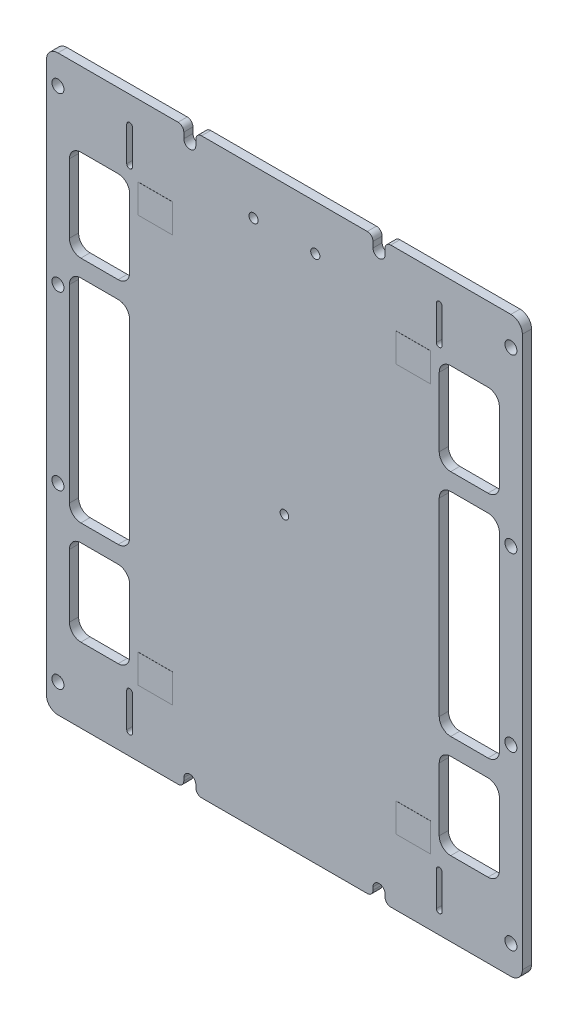
SolidWorks part; units mm, degrees
material "FR4_stuffedProtoboard"
ref_plane "Front Plane" through (0, 0, 0) normal (0, 0, 1) x (1, 0, 0)
ref_plane "Top Plane" through (0, 0, 0) normal (0, 1, 0) x (1, 0, 0)
ref_plane "Right Plane" through (0, 0, 0) normal (1, 0, 0) x (0, 0, -1)
sketch "Sketch1" plane through (0, 0, 0) normal (0, 0, 1) x (1, 0, 0)
  line L1 (-39.5, -50) -> (39.5, -50)
  line L2 (-41.5, -48) -> (-41.5, 48)
  line L3 (-39.5, 50) -> (39.5, 50)
  line L4 (41.5, -48) -> (41.5, 48)
  line L5 (-41.5, -50) -> (41.5, 50) construction
  line L6 (-41.5, 50) -> (41.5, -50) construction
  arc A0 (-39.5, -50) -> (-41.5, -48) centre (-39.5, -48) cw
  arc A1 (39.5, -50) -> (41.5, -48) centre (39.5, -48) ccw
  arc A2 (39.5, 50) -> (41.5, 48) centre (39.5, 48) cw
  arc A3 (-41.5, 48) -> (-39.5, 50) centre (-39.5, 48) cw
  point P0 (0, 0)
  dimension "D3" = 2
  dimension "D1" = 100
  dimension "D2" = 83
extrude "boardOutline" add sketch "Sketch1" along normal blind 1.6
sketch "Sketch2" plane through (0, 0, 1.6) normal (0, 0, 1) x (1, 0, 0)
  line L0 (39.5, 50) -> (-39.5, 50) construction
  line L1 (-41.5, 48) -> (-41.5, -48) construction
  line L2 (-5.385, 42.1) -> (5.385, 42.1) construction
  line L3 (-38, 44.2) -> (-38, 4.2) construction
  line L4 (0, 42.1) -> (0, 50) construction
  circle A0 centre (0, 0) radius 0.75
  circle A1 centre (-38, 44.2) radius 1.05 construction
  circle A2 centre (37.5, 44.2) radius 1.05 construction
  circle A3 centre (37.5, 4.2) radius 1.05 construction
  circle A4 centre (37.5, -35.8) radius 1.05 construction
  circle A5 centre (-38, 4.2) radius 1.05 construction
  circle A6 centre (-38, -35.8) radius 1.05 construction
  circle A7 centre (-5.385, 42.1) radius 0.8
  circle A8 centre (5.385, 42.1) radius 0.8
  dimension "D1" = 1.5
  dimension "D2" = 2.1
  dimension "D9" = 10.77
  dimension "D7" = 1.6
  dimension "D11" = 7.9
  dimension "D3" = 5.8
  dimension "D4" = 3.5
  dimension "D8" = 40
  dimension "D10" = 37.5
  dimension "D5" = 2
  dimension "D6" = 3
extrude "componentHoles" cut sketch "Sketch2" against normal through all
sketch "Sketch4" plane through (0, 0, 1.6) normal (0, 0, 1) x (1, 0, 0)
  line L0 (-27, 39.25) -> (-27, 45.25) construction
  line L1 (-27.5, 39.25) -> (-27.5, 45.25)
  line L2 (-26.5, 39.25) -> (-26.5, 45.25)
  line L3 (39.5, 50) -> (-39.5, 50) construction
  line L4 (-41.5, 48) -> (-41.5, -48) construction
  line L5 (27, 39.25) -> (27, 45.25) construction
  line L6 (26.5, 39.25) -> (26.5, 45.25)
  line L7 (27.5, 39.25) -> (27.5, 45.25)
  line L8 (27, -46.25) -> (27, -40.25) construction
  line L9 (26.5, -46.25) -> (26.5, -40.25)
  line L10 (27.5, -46.25) -> (27.5, -40.25)
  line L11 (-27, -46.25) -> (-27, -40.25) construction
  line L12 (-27.5, -46.25) -> (-27.5, -40.25)
  line L13 (-26.5, -46.25) -> (-26.5, -40.25)
  line L14 (-27, 39.25) -> (27, 39.25) construction
  line L15 (0, 39.25) -> (0, 50) construction
  arc A0 (-27.5, 39.25) -> (-26.5, 39.25) centre (-27, 39.25) ccw
  arc A1 (-26.5, 45.25) -> (-27.5, 45.25) centre (-27, 45.25) ccw
  arc A2 (26.5, 39.25) -> (27.5, 39.25) centre (27, 39.25) ccw
  arc A3 (27.5, 45.25) -> (26.5, 45.25) centre (27, 45.25) ccw
  arc A4 (26.5, -46.25) -> (27.5, -46.25) centre (27, -46.25) ccw
  arc A5 (27.5, -40.25) -> (26.5, -40.25) centre (27, -40.25) ccw
  arc A6 (-27.5, -46.25) -> (-26.5, -46.25) centre (-27, -46.25) ccw
  arc A7 (-26.5, -40.25) -> (-27.5, -40.25) centre (-27, -40.25) ccw
  point P2 (-27, 42.25)
  point P16 (27, 42.25)
  point P23 (27, -43.25)
  point P30 (-27, -43.25)
  dimension "D1" = 4.75
  dimension "D2" = 14
  dimension "D3" = 1
  dimension "D4" = 6
  dimension "D7" = 54
  dimension "D9" = 79.5
  dimension "D5" = 2
  dimension "D6" = 2
extrude "solarCellContactHoles" cut sketch "Sketch4" against normal blind 1.6
sketch "FrameLattice" plane through (0, 0, 0) normal (0, 0, 1) x (1, 0, 0)
  line L4 (-13, -19) -> (13, -19)
  line L5 (15, -17) -> (15, 16)
  line L6 (13, 18) -> (-13, 18)
  line L7 (-15, 16) -> (-15, -17)
  line L8 (-13, -19) -> (13, -19)
  line L9 (15, -17) -> (15, 16)
  line L10 (13, 18) -> (-13, 18)
  line L11 (-15, 16) -> (-15, -17)
  line L12 (-13, -92) -> (13, -92)
  line L13 (15, -90) -> (15, -69)
  line L14 (13, -67) -> (-13, -67)
  line L15 (-15, -69) -> (-15, -90)
  line L16 (-13, -92) -> (13, -92)
  line L17 (15, -90) -> (15, -69)
  line L18 (13, -67) -> (-13, -67)
  line L19 (-15, -69) -> (-15, -90)
  line L20 (-35.5, -132) -> (-20, -132)
  line L21 (-18, -130) -> (-18, -97)
  line L22 (-20, -95) -> (-35.5, -95)
  line L23 (-37.5, -97) -> (-37.5, -130)
  line L24 (-35.5, -132) -> (-20, -132)
  line L25 (-18, -130) -> (-18, -97)
  line L26 (-20, -95) -> (-35.5, -95)
  line L27 (-37.5, -97) -> (-37.5, -130)
  line L28 (20, -160) -> (35.5, -160)
  line L29 (37.5, -158) -> (37.5, -137)
  line L30 (35.5, -135) -> (20, -135)
  line L31 (18, -137) -> (18, -158)
  line L32 (20, -160) -> (35.5, -160)
  line L33 (37.5, -158) -> (37.5, -137)
  line L34 (35.5, -135) -> (20, -135)
  line L35 (18, -137) -> (18, -158)
  line L36 (20, -92) -> (35.5, -92)
  line L37 (37.5, -90) -> (37.5, -69)
  line L38 (35.5, -67) -> (20, -67)
  line L39 (18, -69) -> (18, -90)
  line L40 (20, -92) -> (35.5, -92)
  line L41 (37.5, -90) -> (37.5, -69)
  line L42 (35.5, -67) -> (20, -67)
  line L43 (18, -69) -> (18, -90)
  line L44 (-35.5, -92) -> (-20, -92)
  line L45 (-18, -90) -> (-18, -69)
  line L46 (-20, -67) -> (-35.5, -67)
  line L47 (-37.5, -69) -> (-37.5, -90)
  line L48 (-35.5, -92) -> (-20, -92)
  line L49 (-18, -90) -> (-18, -69)
  line L50 (-20, -67) -> (-35.5, -67)
  line L51 (-37.5, -69) -> (-37.5, -90)
  line L52 (20, -132) -> (35.5, -132)
  line L53 (37.5, -130) -> (37.5, -97)
  line L54 (35.5, -95) -> (20, -95)
  line L55 (18, -97) -> (18, -130)
  line L56 (20, -132) -> (35.5, -132)
  line L57 (37.5, -130) -> (37.5, -97)
  line L58 (35.5, -95) -> (20, -95)
  line L59 (18, -97) -> (18, -130)
  line L60 (-13, -160) -> (13, -160)
  line L61 (15, -158) -> (15, -137)
  line L62 (13, -135) -> (-13, -135)
  line L63 (-15, -137) -> (-15, -158)
  line L65 (15, -158) -> (15, -137)
  line L66 (13, -135) -> (-13, -135)
  line L67 (-15, -137) -> (-15, -158)
  line L68 (-26.75, -62) -> (-26.75, -52)
  line L69 (-28.75, -50) -> (-35, -50)
  line L70 (-37, -52) -> (-37, -62)
  line L71 (-35, -64) -> (-28.75, -64)
  line L72 (-26.75, -62) -> (-26.75, -52)
  line L73 (-28.75, -50) -> (-35, -50)
  line L74 (-37, -52) -> (-37, -62)
  line L75 (-35, -64) -> (-28.75, -64)
  line L76 (-35.5, -160) -> (-20, -160)
  line L77 (-18, -158) -> (-18, -137)
  line L78 (-20, -135) -> (-35.5, -135)
  line L79 (-37.5, -137) -> (-37.5, -158)
  line L80 (-35.5, -160) -> (-20, -160)
  line L81 (-18, -158) -> (-18, -137)
  line L82 (-20, -135) -> (-35.5, -135)
  line L83 (-37.5, -137) -> (-37.5, -158)
  line L84 (-13, -132) -> (13, -132)
  line L85 (15, -130) -> (15, -97)
  line L86 (13, -95) -> (-13, -95)
  line L87 (-15, -97) -> (-15, -130)
  line L88 (-13, -132) -> (13, -132)
  line L89 (15, -130) -> (15, -97)
  line L90 (13, -95) -> (-13, -95)
  line L91 (-15, -97) -> (-15, -130)
  line L92 (-35.5, -19) -> (-20, -19)
  line L93 (-18, -17) -> (-18, 16)
  line L94 (-20, 18) -> (-35.5, 18)
  line L95 (-37.5, 16) -> (-37.5, -17)
  line L96 (-35.5, -19) -> (-20, -19)
  line L97 (-18, -17) -> (-18, 16)
  line L98 (-20, 18) -> (-35.5, 18)
  line L99 (-37.5, 16) -> (-37.5, -17)
  line L100 (20, -47) -> (35.5, -47)
  line L101 (37.5, -45) -> (37.5, -24)
  line L102 (35.5, -22) -> (20, -22)
  line L103 (18, -24) -> (18, -45)
  line L104 (20, -47) -> (35.5, -47)
  line L105 (37.5, -45) -> (37.5, -24)
  line L106 (35.5, -22) -> (20, -22)
  line L107 (18, -24) -> (18, -45)
  line L108 (-13, -47) -> (13, -47)
  line L109 (15, -45) -> (15, -24)
  line L110 (13, -22) -> (-13, -22)
  line L111 (-15, -24) -> (-15, -45)
  line L112 (-13, -47) -> (13, -47)
  line L113 (15, -45) -> (15, -24)
  line L114 (13, -22) -> (-13, -22)
  line L115 (-15, -24) -> (-15, -45)
  line L116 (-35.5, -47) -> (-20, -47)
  line L117 (-18, -45) -> (-18, -24)
  line L118 (-20, -22) -> (-35.5, -22)
  line L119 (-37.5, -24) -> (-37.5, -45)
  line L120 (-35.5, -47) -> (-20, -47)
  line L121 (-18, -45) -> (-18, -24)
  line L122 (-20, -22) -> (-35.5, -22)
  line L123 (-37.5, -24) -> (-37.5, -45)
  line L124 (20, -19) -> (35.5, -19)
  line L125 (37.5, -17) -> (37.5, 16)
  line L126 (35.5, 18) -> (20, 18)
  line L127 (18, 16) -> (18, -17)
  line L128 (20, -19) -> (35.5, -19)
  line L129 (37.5, -17) -> (37.5, 16)
  line L130 (35.5, 18) -> (20, 18)
  line L131 (18, 16) -> (18, -17)
  line L132 (-35.5, 21) -> (-20, 21)
  line L133 (-18, 23) -> (-18, 44)
  line L134 (-20, 46) -> (-35.5, 46)
  line L135 (-37.5, 44) -> (-37.5, 23)
  line L136 (-35.5, 21) -> (-20, 21)
  line L137 (-18, 23) -> (-18, 44)
  line L138 (-20, 46) -> (-35.5, 46)
  line L139 (-37.5, 44) -> (-37.5, 23)
  line L140 (-13, 21) -> (13, 21)
  line L141 (15, 23) -> (15, 44)
  line L142 (13, 46) -> (-13, 46)
  line L143 (-15, 44) -> (-15, 23)
  line L144 (-13, 21) -> (13, 21)
  line L145 (15, 23) -> (15, 44)
  line L147 (-15, 44) -> (-15, 23)
  line L148 (20, 21) -> (35.5, 21)
  line L149 (37.5, 23) -> (37.5, 44)
  line L150 (35.5, 46) -> (20, 46)
  line L151 (18, 44) -> (18, 23)
  line L152 (20, 21) -> (35.5, 21)
  line L153 (37.5, 23) -> (37.5, 44)
  line L154 (35.5, 46) -> (20, 46)
  line L155 (18, 44) -> (18, 23)
  line L156 (-3.5, -62) -> (-3.5, -52)
  line L157 (-5.5, -50) -> (-13, -50)
  line L158 (-15, -52) -> (-15, -62)
  line L159 (-13, -64) -> (-5.5, -64)
  line L160 (-3.5, -62) -> (-3.5, -52)
  line L161 (-5.5, -50) -> (-13, -50)
  line L162 (-15, -52) -> (-15, -62)
  line L163 (-13, -64) -> (-5.5, -64)
  line L164 (28.75, -64) -> (35, -64)
  line L165 (37, -62) -> (37, -52)
  line L166 (35, -50) -> (28.75, -50)
  line L167 (26.75, -52) -> (26.75, -62)
  line L168 (28.75, -64) -> (35, -64)
  line L169 (37, -62) -> (37, -52)
  line L170 (35, -50) -> (28.75, -50)
  line L171 (26.75, -52) -> (26.75, -62)
  line L172 (5.5, -64) -> (13, -64)
  line L173 (15, -62) -> (15, -52)
  line L174 (13, -50) -> (5.5, -50)
  line L175 (3.5, -52) -> (3.5, -62)
  line L176 (5.5, -64) -> (13, -64)
  line L177 (15, -62) -> (15, -52)
  line L178 (13, -50) -> (5.5, -50)
  line L179 (3.5, -52) -> (3.5, -62)
  line L212 (-13, -160) -> (13, -160)
  line L213 (13, 46) -> (-13, 46)
  circle A2 centre (-16.5, 48) radius 0.8
  circle A3 centre (-16.5, 48) radius 0.8
  circle A4 centre (-16.5, -162) radius 0.8
  arc A5 (13, -19) -> (15, -17) centre (13, -17) ccw
  arc A6 (15, 16) -> (13, 18) centre (13, 16) ccw
  arc A7 (-13, 18) -> (-15, 16) centre (-13, 16) ccw
  arc A8 (-15, -17) -> (-13, -19) centre (-13, -17) ccw
  arc A9 (13, -19) -> (15, -17) centre (13, -17) ccw
  arc A10 (15, 16) -> (13, 18) centre (13, 16) ccw
  arc A11 (-13, 18) -> (-15, 16) centre (-13, 16) ccw
  arc A12 (-15, -17) -> (-13, -19) centre (-13, -17) ccw
  arc A13 (13, -92) -> (15, -90) centre (13, -90) ccw
  arc A14 (15, -69) -> (13, -67) centre (13, -69) ccw
  arc A15 (-13, -67) -> (-15, -69) centre (-13, -69) ccw
  arc A16 (-15, -90) -> (-13, -92) centre (-13, -90) ccw
  arc A17 (13, -92) -> (15, -90) centre (13, -90) ccw
  arc A18 (15, -69) -> (13, -67) centre (13, -69) ccw
  arc A19 (-13, -67) -> (-15, -69) centre (-13, -69) ccw
  arc A20 (-15, -90) -> (-13, -92) centre (-13, -90) ccw
  arc A21 (-20, -132) -> (-18, -130) centre (-20, -130) ccw
  arc A22 (-18, -97) -> (-20, -95) centre (-20, -97) ccw
  arc A23 (-35.5, -95) -> (-37.5, -97) centre (-35.5, -97) ccw
  arc A24 (-37.5, -130) -> (-35.5, -132) centre (-35.5, -130) ccw
  arc A25 (-20, -132) -> (-18, -130) centre (-20, -130) ccw
  arc A26 (-18, -97) -> (-20, -95) centre (-20, -97) ccw
  arc A27 (-35.5, -95) -> (-37.5, -97) centre (-35.5, -97) ccw
  arc A28 (-37.5, -130) -> (-35.5, -132) centre (-35.5, -130) ccw
  arc A29 (35.5, -160) -> (37.5, -158) centre (35.5, -158) ccw
  arc A30 (37.5, -137) -> (35.5, -135) centre (35.5, -137) ccw
  arc A31 (20, -135) -> (18, -137) centre (20, -137) ccw
  arc A32 (18, -158) -> (20, -160) centre (20, -158) ccw
  arc A33 (35.5, -160) -> (37.5, -158) centre (35.5, -158) ccw
  arc A34 (37.5, -137) -> (35.5, -135) centre (35.5, -137) ccw
  arc A35 (20, -135) -> (18, -137) centre (20, -137) ccw
  arc A36 (18, -158) -> (20, -160) centre (20, -158) ccw
  arc A37 (35.5, -92) -> (37.5, -90) centre (35.5, -90) ccw
  arc A38 (37.5, -69) -> (35.5, -67) centre (35.5, -69) ccw
  arc A39 (20, -67) -> (18, -69) centre (20, -69) ccw
  arc A40 (18, -90) -> (20, -92) centre (20, -90) ccw
  arc A41 (35.5, -92) -> (37.5, -90) centre (35.5, -90) ccw
  arc A42 (37.5, -69) -> (35.5, -67) centre (35.5, -69) ccw
  arc A43 (20, -67) -> (18, -69) centre (20, -69) ccw
  arc A44 (18, -90) -> (20, -92) centre (20, -90) ccw
  arc A45 (-20, -92) -> (-18, -90) centre (-20, -90) ccw
  arc A46 (-18, -69) -> (-20, -67) centre (-20, -69) ccw
  arc A47 (-35.5, -67) -> (-37.5, -69) centre (-35.5, -69) ccw
  arc A48 (-37.5, -90) -> (-35.5, -92) centre (-35.5, -90) ccw
  arc A49 (-20, -92) -> (-18, -90) centre (-20, -90) ccw
  arc A50 (-18, -69) -> (-20, -67) centre (-20, -69) ccw
  arc A51 (-35.5, -67) -> (-37.5, -69) centre (-35.5, -69) ccw
  arc A52 (-37.5, -90) -> (-35.5, -92) centre (-35.5, -90) ccw
  arc A53 (35.5, -132) -> (37.5, -130) centre (35.5, -130) ccw
  arc A54 (37.5, -97) -> (35.5, -95) centre (35.5, -97) ccw
  arc A55 (20, -95) -> (18, -97) centre (20, -97) ccw
  arc A56 (18, -130) -> (20, -132) centre (20, -130) ccw
  arc A57 (35.5, -132) -> (37.5, -130) centre (35.5, -130) ccw
  arc A58 (37.5, -97) -> (35.5, -95) centre (35.5, -97) ccw
  arc A59 (20, -95) -> (18, -97) centre (20, -97) ccw
  arc A60 (18, -130) -> (20, -132) centre (20, -130) ccw
  arc A61 (13, -160) -> (15, -158) centre (13, -158) ccw
  arc A62 (15, -137) -> (13, -135) centre (13, -137) ccw
  arc A63 (-13, -135) -> (-15, -137) centre (-13, -137) ccw
  arc A64 (-15, -158) -> (-13, -160) centre (-13, -158) ccw
  arc A65 (13, -160) -> (15, -158) centre (13, -158) ccw
  arc A66 (15, -137) -> (13, -135) centre (13, -137) ccw
  arc A67 (-13, -135) -> (-15, -137) centre (-13, -137) ccw
  arc A68 (-15, -158) -> (-13, -160) centre (-13, -158) ccw
  circle A69 centre (-16.5, -162) radius 0.8
  circle A70 centre (16.5, -162) radius 0.8
  circle A71 centre (16.5, -162) radius 0.8
  circle A72 centre (-16.5, -65.5) radius 0.8
  circle A73 centre (-16.5, -65.5) radius 0.8
  circle A74 centre (16.5, -65.5) radius 0.8
  circle A75 centre (16.5, -65.5) radius 0.8
  circle A76 centre (-39.5, -129) radius 0.8
  circle A77 centre (-39.5, -129) radius 0.8
  circle A78 centre (39.5, -159) radius 0.8
  circle A79 centre (39.5, -159) radius 0.8
  circle A80 centre (-39.5, -159) radius 0.8
  circle A81 centre (-39.5, -159) radius 0.8
  circle A82 centre (39.5, -129) radius 0.8
  circle A83 centre (39.5, -129) radius 0.8
  circle A84 centre (39.5, -99) radius 0.8
  circle A85 centre (39.5, -99) radius 0.8
  circle A86 centre (-39.5, -99) radius 0.8
  circle A87 centre (-39.5, -99) radius 0.8
  circle A88 centre (-39.5, -69) radius 0.8
  circle A89 centre (-39.5, -69) radius 0.8
  circle A90 centre (39.5, -69) radius 0.8
  circle A91 centre (39.5, -69) radius 0.8
  circle A92 centre (39.5, -15) radius 0.8
  circle A93 centre (39.5, -15) radius 0.8
  circle A94 centre (39.5, 15) radius 0.8
  arc A95 (-26.75, -52) -> (-28.75, -50) centre (-28.75, -52) ccw
  arc A96 (-35, -50) -> (-37, -52) centre (-35, -52) ccw
  arc A97 (-37, -62) -> (-35, -64) centre (-35, -62) ccw
  arc A98 (-28.75, -64) -> (-26.75, -62) centre (-28.75, -62) ccw
  arc A99 (-26.75, -52) -> (-28.75, -50) centre (-28.75, -52) ccw
  arc A100 (-35, -50) -> (-37, -52) centre (-35, -52) ccw
  arc A101 (-37, -62) -> (-35, -64) centre (-35, -62) ccw
  arc A102 (-28.75, -64) -> (-26.75, -62) centre (-28.75, -62) ccw
  arc A103 (-20, -160) -> (-18, -158) centre (-20, -158) ccw
  arc A104 (-18, -137) -> (-20, -135) centre (-20, -137) ccw
  arc A105 (-35.5, -135) -> (-37.5, -137) centre (-35.5, -137) ccw
  arc A106 (-37.5, -158) -> (-35.5, -160) centre (-35.5, -158) ccw
  arc A107 (-20, -160) -> (-18, -158) centre (-20, -158) ccw
  arc A108 (-18, -137) -> (-20, -135) centre (-20, -137) ccw
  arc A109 (-35.5, -135) -> (-37.5, -137) centre (-35.5, -137) ccw
  arc A110 (-37.5, -158) -> (-35.5, -160) centre (-35.5, -158) ccw
  arc A111 (13, -132) -> (15, -130) centre (13, -130) ccw
  arc A112 (15, -97) -> (13, -95) centre (13, -97) ccw
  arc A113 (-13, -95) -> (-15, -97) centre (-13, -97) ccw
  arc A114 (-15, -130) -> (-13, -132) centre (-13, -130) ccw
  arc A115 (13, -132) -> (15, -130) centre (13, -130) ccw
  arc A116 (15, -97) -> (13, -95) centre (13, -97) ccw
  arc A117 (-13, -95) -> (-15, -97) centre (-13, -97) ccw
  arc A118 (-15, -130) -> (-13, -132) centre (-13, -130) ccw
  arc A119 (-20, -19) -> (-18, -17) centre (-20, -17) ccw
  arc A120 (-18, 16) -> (-20, 18) centre (-20, 16) ccw
  arc A121 (-35.5, 18) -> (-37.5, 16) centre (-35.5, 16) ccw
  arc A122 (-37.5, -17) -> (-35.5, -19) centre (-35.5, -17) ccw
  arc A123 (-20, -19) -> (-18, -17) centre (-20, -17) ccw
  arc A124 (-18, 16) -> (-20, 18) centre (-20, 16) ccw
  arc A125 (-35.5, 18) -> (-37.5, 16) centre (-35.5, 16) ccw
  arc A126 (-37.5, -17) -> (-35.5, -19) centre (-35.5, -17) ccw
  arc A127 (35.5, -47) -> (37.5, -45) centre (35.5, -45) ccw
  arc A128 (37.5, -24) -> (35.5, -22) centre (35.5, -24) ccw
  arc A129 (20, -22) -> (18, -24) centre (20, -24) ccw
  arc A130 (18, -45) -> (20, -47) centre (20, -45) ccw
  arc A131 (35.5, -47) -> (37.5, -45) centre (35.5, -45) ccw
  arc A132 (37.5, -24) -> (35.5, -22) centre (35.5, -24) ccw
  arc A133 (20, -22) -> (18, -24) centre (20, -24) ccw
  arc A134 (18, -45) -> (20, -47) centre (20, -45) ccw
  arc A135 (13, -47) -> (15, -45) centre (13, -45) ccw
  arc A136 (15, -24) -> (13, -22) centre (13, -24) ccw
  arc A137 (-13, -22) -> (-15, -24) centre (-13, -24) ccw
  arc A138 (-15, -45) -> (-13, -47) centre (-13, -45) ccw
  arc A139 (13, -47) -> (15, -45) centre (13, -45) ccw
  arc A140 (15, -24) -> (13, -22) centre (13, -24) ccw
  arc A141 (-13, -22) -> (-15, -24) centre (-13, -24) ccw
  arc A142 (-15, -45) -> (-13, -47) centre (-13, -45) ccw
  arc A143 (-20, -47) -> (-18, -45) centre (-20, -45) ccw
  arc A144 (-18, -24) -> (-20, -22) centre (-20, -24) ccw
  arc A145 (-35.5, -22) -> (-37.5, -24) centre (-35.5, -24) ccw
  arc A146 (-37.5, -45) -> (-35.5, -47) centre (-35.5, -45) ccw
  arc A147 (-20, -47) -> (-18, -45) centre (-20, -45) ccw
  arc A148 (-18, -24) -> (-20, -22) centre (-20, -24) ccw
  arc A149 (-35.5, -22) -> (-37.5, -24) centre (-35.5, -24) ccw
  arc A150 (-37.5, -45) -> (-35.5, -47) centre (-35.5, -45) ccw
  arc A151 (35.5, -19) -> (37.5, -17) centre (35.5, -17) ccw
  arc A152 (37.5, 16) -> (35.5, 18) centre (35.5, 16) ccw
  arc A153 (20, 18) -> (18, 16) centre (20, 16) ccw
  arc A154 (18, -17) -> (20, -19) centre (20, -17) ccw
  arc A155 (35.5, -19) -> (37.5, -17) centre (35.5, -17) ccw
  arc A156 (37.5, 16) -> (35.5, 18) centre (35.5, 16) ccw
  arc A157 (20, 18) -> (18, 16) centre (20, 16) ccw
  arc A158 (18, -17) -> (20, -19) centre (20, -17) ccw
  arc A159 (-20, 21) -> (-18, 23) centre (-20, 23) ccw
  arc A160 (-18, 44) -> (-20, 46) centre (-20, 44) ccw
  arc A161 (-35.5, 46) -> (-37.5, 44) centre (-35.5, 44) ccw
  arc A162 (-37.5, 23) -> (-35.5, 21) centre (-35.5, 23) ccw
  arc A163 (-20, 21) -> (-18, 23) centre (-20, 23) ccw
  arc A164 (-18, 44) -> (-20, 46) centre (-20, 44) ccw
  arc A165 (-35.5, 46) -> (-37.5, 44) centre (-35.5, 44) ccw
  arc A166 (-37.5, 23) -> (-35.5, 21) centre (-35.5, 23) ccw
  arc A167 (13, 21) -> (15, 23) centre (13, 23) ccw
  arc A168 (15, 44) -> (13, 46) centre (13, 44) ccw
  arc A169 (-13, 46) -> (-15, 44) centre (-13, 44) ccw
  arc A170 (-15, 23) -> (-13, 21) centre (-13, 23) ccw
  arc A171 (13, 21) -> (15, 23) centre (13, 23) ccw
  arc A172 (15, 44) -> (13, 46) centre (13, 44) ccw
  arc A173 (-13, 46) -> (-15, 44) centre (-13, 44) ccw
  arc A174 (-15, 23) -> (-13, 21) centre (-13, 23) ccw
  arc A175 (35.5, 21) -> (37.5, 23) centre (35.5, 23) ccw
  arc A176 (37.5, 44) -> (35.5, 46) centre (35.5, 44) ccw
  arc A177 (20, 46) -> (18, 44) centre (20, 44) ccw
  arc A178 (18, 23) -> (20, 21) centre (20, 23) ccw
  arc A179 (35.5, 21) -> (37.5, 23) centre (35.5, 23) ccw
  arc A180 (37.5, 44) -> (35.5, 46) centre (35.5, 44) ccw
  arc A181 (20, 46) -> (18, 44) centre (20, 44) ccw
  arc A182 (18, 23) -> (20, 21) centre (20, 23) ccw
  circle A183 centre (39.5, 15) radius 0.8
  circle A184 centre (-39.5, 45) radius 0.8
  circle A185 centre (-39.5, 45) radius 0.8
  circle A186 centre (39.5, 45) radius 0.8
  circle A187 centre (39.5, 45) radius 0.8
  circle A188 centre (-39.5, 15) radius 0.8
  circle A189 centre (-39.5, 15) radius 0.8
  circle A190 centre (16.5, -48.5) radius 0.8
  circle A191 centre (16.5, -48.5) radius 0.8
  circle A192 centre (-16.5, -48.5) radius 0.8
  circle A193 centre (-16.5, -48.5) radius 0.8
  circle A194 centre (16.5, 48) radius 0.8
  circle A195 centre (16.5, 48) radius 0.8
  circle A196 centre (-39.5, -15) radius 0.8
  circle A197 centre (-39.5, -15) radius 0.8
  circle A198 centre (-22, -61) radius 2.75
  circle A199 centre (-22, -61) radius 2.75
  circle A200 centre (-22, -53) radius 2.75
  circle A201 centre (-22, -53) radius 2.75
  circle A202 centre (22, -53) radius 2.75
  circle A203 centre (22, -53) radius 2.75
  circle A204 centre (22, -61) radius 2.75
  arc A205 (-3.5, -52) -> (-5.5, -50) centre (-5.5, -52) ccw
  arc A206 (-13, -50) -> (-15, -52) centre (-13, -52) ccw
  arc A207 (-15, -62) -> (-13, -64) centre (-13, -62) ccw
  arc A208 (-5.5, -64) -> (-3.5, -62) centre (-5.5, -62) ccw
  arc A209 (-3.5, -52) -> (-5.5, -50) centre (-5.5, -52) ccw
  arc A210 (-13, -50) -> (-15, -52) centre (-13, -52) ccw
  arc A211 (-15, -62) -> (-13, -64) centre (-13, -62) ccw
  arc A212 (-5.5, -64) -> (-3.5, -62) centre (-5.5, -62) ccw
  circle A213 centre (22, -61) radius 2.75
  circle A214 centre (0, -57) radius 2.75
  circle A215 centre (0, -57) radius 2.75
  circle A216 centre (39.5, -45) radius 0.8
  circle A217 centre (39.5, -45) radius 0.8
  circle A218 centre (-39.5, -45) radius 0.8
  arc A219 (35, -64) -> (37, -62) centre (35, -62) ccw
  arc A220 (37, -52) -> (35, -50) centre (35, -52) ccw
  arc A221 (28.75, -50) -> (26.75, -52) centre (28.75, -52) ccw
  arc A222 (26.75, -62) -> (28.75, -64) centre (28.75, -62) ccw
  arc A223 (35, -64) -> (37, -62) centre (35, -62) ccw
  arc A224 (37, -52) -> (35, -50) centre (35, -52) ccw
  arc A225 (28.75, -50) -> (26.75, -52) centre (28.75, -52) ccw
  arc A226 (26.75, -62) -> (28.75, -64) centre (28.75, -62) ccw
  arc A227 (13, -64) -> (15, -62) centre (13, -62) ccw
  arc A228 (15, -52) -> (13, -50) centre (13, -52) ccw
  arc A229 (5.5, -50) -> (3.5, -52) centre (5.5, -52) ccw
  arc A230 (3.5, -62) -> (5.5, -64) centre (5.5, -62) ccw
  arc A231 (13, -64) -> (15, -62) centre (13, -62) ccw
  arc A232 (15, -52) -> (13, -50) centre (13, -52) ccw
  arc A233 (5.5, -50) -> (3.5, -52) centre (5.5, -52) ccw
  arc A234 (3.5, -62) -> (5.5, -64) centre (5.5, -62) ccw
  circle A235 centre (-39.5, -45) radius 0.8
  dimension "D1" = 0
  dimension "D2" = 0
  dimension "D3" = 0
  dimension "D4" = 0
  dimension "D5" = 0
  dimension "D6" = 0
  dimension "D7" = 0
  dimension "D8" = 0
  dimension "D9" = 0
  dimension "D10" = 0
  dimension "D11" = 0
  dimension "D12" = 0
  dimension "D13" = 0
  dimension "D14" = 0
  dimension "D15" = 0
  dimension "D16" = 0
  dimension "D17" = 0
  dimension "D18" = 0
  dimension "D19" = 0
  dimension "D20" = 0
  dimension "D21" = 0
  dimension "D22" = 0
  dimension "D23" = 0
  dimension "D24" = 0
  dimension "D25" = 0
  dimension "D26" = 0
  dimension "D27" = 0
  dimension "D28" = 0
  dimension "D29" = 0
  dimension "D30" = 0
  dimension "D31" = 0
  dimension "D32" = 0
  dimension "D33" = 0
  dimension "D34" = 0
  dimension "D35" = 0
  dimension "D36" = 0
  dimension "D37" = 0
  dimension "D38" = 0
  dimension "D39" = 0
  dimension "D40" = 0
  dimension "D41" = 0
  dimension "D42" = 0
  dimension "D43" = 0
  dimension "D44" = 0
  dimension "D45" = 0
  dimension "D46" = 0
  dimension "D47" = 0
  dimension "D48" = 0
  dimension "D49" = 0
  dimension "D50" = 0
  dimension "D51" = 0
sketch "Sketch3" plane through (0, 0, 1.6) normal (0, 0, 1) x (1, 0, 0)
  line L0 (-35.5, -19) -> (-20, -19) construction
  line L1 (-35.5, 37) -> (-29, 37)
  line L2 (-37.5, 35) -> (-37.5, 23)
  line L3 (-35.5, 21) -> (-29, 21)
  line L4 (-27, 35) -> (-27, 23)
  line L6 (-29, -22) -> (-35.5, -22)
  line L7 (-37.5, 16) -> (-37.5, -17) construction
  line L8 (-20, -22) -> (-35.5, -22) construction
  line L9 (0, 50) -> (0, -50) construction
  line L10 (39.5, 50) -> (-39.5, 50) construction
  line L11 (-39.5, -50) -> (39.5, -50) construction
  line L12 (-27, -24) -> (-27, -35)
  line L13 (-29, -37) -> (-35.5, -37)
  line L14 (-37.5, -24) -> (-37.5, -35)
  line L15 (-20, 18) -> (-35.5, 18) construction
  line L16 (-35.5, 21) -> (-20, 21) construction
  line L19 (-29, -19) -> (-35.5, -19)
  line L25 (-27, -17) -> (-27, 16)
  line L26 (-29, 18) -> (-35.5, 18)
  line L27 (-37.5, -17) -> (-37.5, 16)
  arc A0 (-37.5, 23) -> (-35.5, 21) centre (-35.5, 23) ccw
  arc A1 (-29, 21) -> (-27, 23) centre (-29, 23) ccw
  arc A2 (-29, 37) -> (-27, 35) centre (-29, 35) cw
  arc A3 (-35.5, 37) -> (-37.5, 35) centre (-35.5, 35) ccw
  arc A4 (-29, -19) -> (-27, -17) centre (-29, -17) ccw
  arc A5 (-27, -35) -> (-29, -37) centre (-29, -35) cw
  arc A6 (-35.5, -37) -> (-37.5, -35) centre (-35.5, -35) cw
  arc A7 (-35.5, -22) -> (-37.5, -24) centre (-35.5, -24) ccw
  arc A8 (-29, -22) -> (-27, -24) centre (-29, -24) cw
  arc A9 (-37.5, 23) -> (-35.5, 21) centre (-35.5, 23) ccw construction
  arc A17 (-35.5, -19) -> (-37.5, -17) centre (-35.5, -17) cw
  arc A18 (-35.5, 18) -> (-37.5, 16) centre (-35.5, 16) ccw
  arc A19 (-27, 16) -> (-29, 18) centre (-29, 16) ccw
  point P12 (-27, 21)
  point P15 (-27, 37)
  point P18 (-37.5, 37)
  dimension "D10" = 13
  dimension "D1" = 10.5
  dimension "D3" = 13
extrude "windows_1side" cut sketch "Sketch3" against normal through all
sketch "Sketch5" plane through (0, 0, 1.6) normal (0, 0, 1) x (1, 0, 0)
  line L0 (-41.5, 48) -> (-41.5, -48) construction
  line L1 (-25.5, 37.5) -> (-19.5, 37.5)
  line L2 (-25.5, 37.5) -> (-25.5, 32.5)
  line L3 (-25.5, 32.5) -> (-19.5, 32.5)
  line L4 (-19.5, 37.5) -> (-19.5, 32.5)
  line L5 (0, 37.5) -> (0, 50) construction
  line L6 (19.5, 37.5) -> (19.5, 32.5)
  line L7 (25.5, 37.5) -> (25.5, 32.5)
  line L8 (19.5, 32.5) -> (25.5, 32.5)
  line L9 (19.5, 37.5) -> (25.5, 37.5)
  line L10 (19.5, -33.5) -> (19.5, -38.5)
  line L11 (25.5, -33.5) -> (25.5, -38.5)
  line L12 (19.5, -38.5) -> (25.5, -38.5)
  line L13 (19.5, -33.5) -> (25.5, -33.5)
  line L14 (-25.5, -33.5) -> (-25.5, -38.5)
  line L15 (-19.5, -33.5) -> (-19.5, -38.5)
  line L16 (-25.5, -38.5) -> (-19.5, -38.5)
  line L17 (-25.5, -33.5) -> (-19.5, -33.5)
  line L18 (-19.5, 37.5) -> (19.5, 37.5) construction
  line L19 (-25.5, 37.5) -> (-25.5, -33.5) construction
  line L20 (39.5, 50) -> (-39.5, 50) construction
  arc A0 (-27.5, 39.25) -> (-26.5, 39.25) centre (-27, 39.25) ccw construction
  dimension "D1" = 5
  dimension "D2" = 6
  dimension "D3" = 16
  dimension "D4" = 1.75
  dimension "D7" = 45
  dimension "D8" = 71
  dimension "D5" = 2
  dimension "D6" = 2
extrude "contactPads" add sketch "Sketch5" along normal blind 0.02
hole_wizard "M2 Clearance Hole1" positions "Sketch6" profile "Sketch7" hole size "M2" standard "ANSI Metric" end condition through all
sketch "Sketch6" plane through (0, 0, 0) normal (0, 0, -1) x (-1, 0, 0)
  line L5 (39.5, -50) -> (39.5, -45) construction
  line L6 (39.5, -50) -> (-39.5, -50) construction
  line L7 (39.5, -45) -> (39.5, -15) construction
  line L8 (39.5, -15) -> (39.5, 15) construction
  line L9 (39.5, 15) -> (39.5, 45) construction
  line L10 (39.5, 45) -> (39.5, 50) construction
  line L11 (-39.5, 50) -> (39.5, 50) construction
  line L15 (37.5, -27.0602) -> (41.5, -27.0602) construction
  line L16 (37.5, -24) -> (37.5, -35) construction
  line L17 (41.5, 48) -> (41.5, -48) construction
  point P0 (39.5, 45)
  point P27 (39.5, -15)
  point P36 (39.5, -45)
  point P38 (39.5, 15)
  point P73 (39.5, -27.0602)
  dimension "D2" = 5
sketch "Sketch7" plane through (-39.5, 45, 0) normal (1, 0, 0) x (0, 1, 0)
  line L0 (0, 0) -> (0, 1.62)
  line L1 (0, 1.62) -> (1.05, 1.62)
  line L2 (1.05, 1.62) -> (1.05, 0)
  line L5 (1.05, 0) -> (0, 0)
  line L11 (0, -6.35) -> (0, 107.95) construction
  dimension "Thru Hole Dia." = 2.1
  dimension "Thru Hole Depth" = 1.62
sketch "Sketch10" plane through (0, 0, 0) normal (0, 0, -1) x (-1, 0, 0)
  line L0 (16.5, 48) -> (16.5, 55.0732) construction
  line L1 (15.45, 48) -> (15.45, 55.0732)
  line L2 (17.55, 48) -> (17.55, 55.0732)
  line L3 (16.5, -48.5) -> (16.5, -55.5732) construction
  line L4 (17.55, -48.5) -> (17.55, -55.5732)
  line L5 (15.45, -48.5) -> (15.45, -55.5732)
  line L6 (41.5, 48) -> (41.5, -48) construction
  line L8 (39.5, -50) -> (-39.5, -50) construction
  line L9 (-39.5, 50) -> (39.5, 50) construction
  arc A0 (15.45, 48) -> (17.55, 48) centre (16.5, 48) ccw
  arc A1 (17.55, 55.0732) -> (15.45, 55.0732) centre (16.5, 55.0732) ccw
  arc A2 (17.55, -48.5) -> (15.45, -48.5) centre (16.5, -48.5) ccw
  arc A3 (15.45, -55.5732) -> (17.55, -55.5732) centre (16.5, -55.5732) ccw
  point P2 (16.5, 51.5366)
  point P7 (16.5, -52.0366)
  dimension "D1" = 1.05
  dimension "D2" = 25
  dimension "D3" = 2
  dimension "D4" = 1.5
extrude "Cut-Extrude1" cut sketch "Sketch10" against normal through all both and the other way through all
fillet "Fillet3" radius 1 4 edges at (-17.55, 50, 0.8) (-15.45, 50, 0.8) (-15.45, -50, 0.8) (-17.55, -50, 0.8)
mirror "Mirror1" about plane through (0, 0, 0) normal (1, 0, 0) of "Cut-Extrude1", "Fillet3", "windows_1side", "M2 Clearance Hole1"
